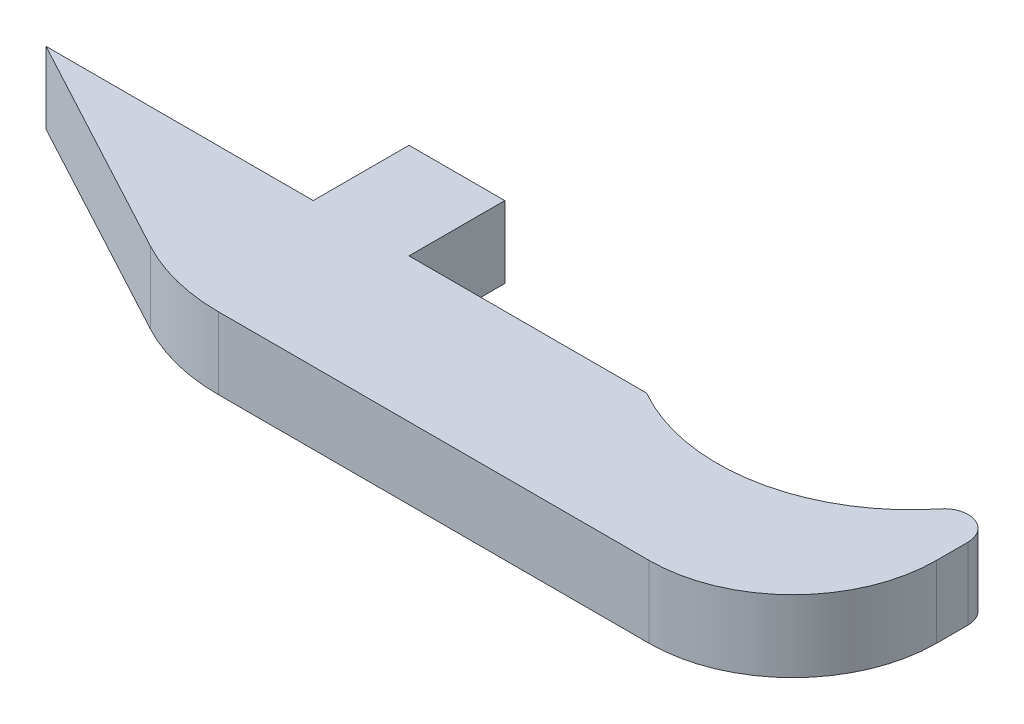
SolidWorks part; units mm, degrees
material "AISI 4130 Steel, annealed at 865C"
ref_plane "X-Y Datum" through (0, 0, 0) normal (0, 0, 1) x (1, 0, 0)
ref_plane "X-Z Datum" through (0, 0, 0) normal (0, 1, 0) x (1, 0, 0)
ref_plane "Y-Z Datum" through (0, 0, 0) normal (1, 0, 0) x (0, 0, -1)
sketch "Sketch1" plane through (0, 0, 0) normal (0, 1, 0) x (1, 0, 0)
  line L0 (20.8895, 0) -> (0, 0) construction
  line L1 (49.3776, 0) -> (0, 0)
  line L2 (49.3776, 0) -> (49.3776, 11.1252)
  line L3 (20.9296, -9.525) -> (62.2046, -9.525)
  line L4 (62.2046, 11.1252) -> (62.2046, -9.525)
  line L5 (3.175, 0) -> (20.9296, -9.525)
  circle A0 centre (49.3776, 11.1252) radius 12.827
  dimension "D3" = 25.654
  dimension "D5" = 9.525
  dimension "D1" = 49.3776
  dimension "D2" = 11.1252
  dimension "D4" = 3.175
  dimension "D6" = 41.275
extrude "Boss-Extrude1" add sketch "Sketch1" along normal blind 4.7625 contours L1 A0 region at (37.4995, 0, 4.291)
fillet "Fillet1" radius 9.525 1 edges at (62.2046, 2.3813, 9.525)
fillet "Fillet2" radius 1.5875 1 edges at (62.2046, 2.3813, -11.1252)
fillet "Fillet4" radius 12.7 1 edges at (20.9296, 2.3813, 9.525)
sketch "Sketch2" plane through (0, 0, 0) normal (0, -1, 0) x (1, 0, 0)
  line L1 (27.2395, -6.35) -> (27.2395, 0)
  line L2 (-7.0505, -6.35) -> (25.8501, -6.35) construction
  line L3 (27.2395, 0) -> (20.8895, 0)
  line L4 (27.2395, 0) -> (27.2395, -6.35)
  line L5 (27.2395, -6.35) -> (20.8895, -6.35)
  line L6 (20.8895, 0) -> (20.8895, -6.35)
  line L7 (33.5895, 0) -> (33.5895, -6.35) construction
  line M6 (3.175, 0) -> (42.9931, 0)
  dimension "D1" = 6.35
  dimension "D2" = 6.35
extrude "Boss-Extrude2" add sketch "Sketch2" against normal blind 4.7625 contours L6 L5 L1 M6 region at (24.0645, 0, -3.175)
